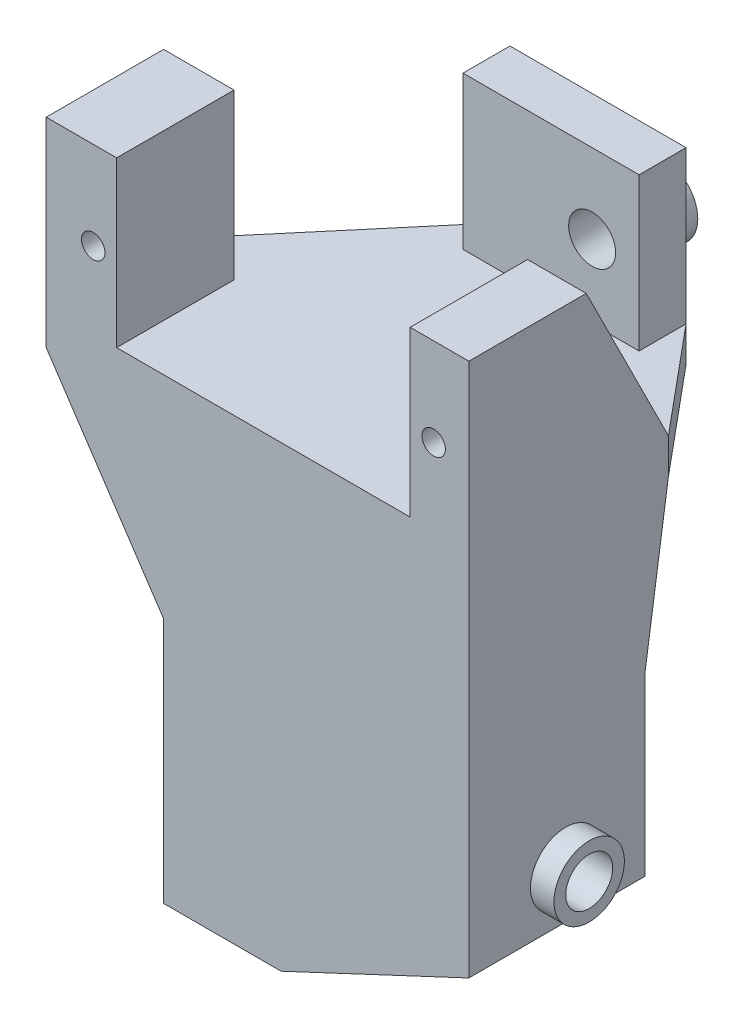
SolidWorks part; units mm, degrees
ref_plane "Front Plane" through (0, 0, 0) normal (0, 0, 1) x (1, 0, 0)
ref_plane "Top Plane" through (0, 0, 0) normal (0, 1, 0) x (1, 0, 0)
ref_plane "Right Plane" through (0, 0, 0) normal (1, 0, 0) x (0, 0, -1)
sketch "Sketch1" plane through (0, 0, 0) normal (0, 1, 0) x (1, 0, 0)
  line L1 (-25, 18) -> (25, 18)
  line L2 (-25, 18) -> (-25, -18)
  line L3 (-25, -18) -> (25, -18)
  line L4 (25, 18) -> (25, -18)
  point P4 (0, 18)
  point P6 (-25, 0)
  dimension "D1" = 50
  dimension "D2" = 36
extrude "Boss-Extrude1" add sketch "Sketch1" along normal blind 3
sketch "Sketch2" plane through (0, 3, 0) normal (0, 1, 0) x (1, 0, 0)
  line L0 (-25, -18) -> (25, -18) construction
  line L1 (25, -8) -> (20, -8)
  line L2 (25, -8) -> (25, 2)
  line L3 (25, 2) -> (20, 2)
  line L4 (20, -8) -> (20, 2)
  line L5 (-5, -8) -> (-11, -8)
  line L6 (-5, -8) -> (-5, 2)
  line L7 (-5, 2) -> (-11, 2)
  line L8 (-11, -8) -> (-11, 2)
  line L9 (25, -18) -> (25, 18) construction
  dimension "D1" = 25
  dimension "D2" = 10
  dimension "D3" = 10
  dimension "D4" = 5
  dimension "D5" = 0
  dimension "D6" = 10
  dimension "D7" = 6
extrude "Boss-Extrude2" add sketch "Sketch2" along normal blind 14
sketch "Sketch3" plane through (0, 3, 0) normal (0, 1, 0) x (1, 0, 0)
  line L0 (20, -8) -> (25, -8) construction
  line L1 (2.5, 14) -> (17.5, 14)
  line L2 (2.5, 14) -> (2.5, 18)
  line L3 (2.5, 18) -> (17.5, 18)
  line L4 (17.5, 14) -> (17.5, 18)
  line L5 (25, 2) -> (25, 18) construction
  dimension "D1" = 22
  dimension "D2" = 4
  dimension "D3" = 15
  dimension "D4" = 7.5
extrude "Boss-Extrude3" add sketch "Sketch3" along normal blind 13
sketch "Sketch4" plane through (0, 0, -18) normal (0, 0, -1) x (-1, 0, 0)
  line L0 (-25, 3) -> (-25, 0) construction
  line L2 (-25, 3) -> (-17.5, 3) construction
  circle A0 centre (-13.5, 9.25) radius 3
  dimension "D1" = 11.5
  dimension "D2" = 6.25
  dimension "D3" = 6
extrude "Boss-Extrude4" add sketch "Sketch4" along normal blind 2 contours A0
sketch "Sketch5" plane through (0, 0, -20) normal (0, 0, -1) x (-1, 0, 0)
  circle A0 centre (-13.5, 9.25) radius 2
  dimension "D1" = 4
extrude "Cut-Extrude1" cut sketch "Sketch5" against normal blind 12
sketch "Sketch6" plane through (0, 3, 0) normal (0, 1, 0) x (1, 0, 0)
  line L0 (-11, 2) -> (-11, 18)
  line L1 (2.5, 18) -> (-25, 18) construction
  line L2 (-11, 18) -> (-25, 18)
  line L3 (-25, 18) -> (-25, -18)
  line L4 (-25, -18) -> (25, -18)
  line L5 (25, -18) -> (25, -8)
  line L6 (25, -8) -> (-11, -8)
  line L7 (-11, -8) -> (-11, 2)
extrude "Cut-Extrude2" cut sketch "Sketch6" against normal blind 11
sketch "Sketch15" plane through (0, 0, 8) normal (0, 0, 1) x (1, 0, 0)
  line L1 (-5, 17) -> (-5, 3) construction
  line L4 (20, 3) -> (-5, 3) construction
  circle A0 centre (-7, 9.5) radius 1
  circle A1 centre (22, 9.5) radius 1
  dimension "D1" = 2
  dimension "D4" = 2
  dimension "D2" = 6.5
  dimension "D3" = 29
extrude "Cut-Extrude9" cut sketch "Sketch15" against normal blind 6
sketch "Sketch16" plane through (0, 0, 8) normal (0, 0, 1) x (1, 0, 0)
  line L0 (25, 17) -> (25, 0) construction
  line L1 (-11, 0) -> (25, 0)
  line L2 (-11, 0) -> (-11, -36)
  line L3 (-11, -36) -> (25, -36)
  line L4 (25, 0) -> (25, -36)
  dimension "D1" = 36
extrude "Boss-Extrude8" add sketch "Sketch16" against normal blind 2
sketch "Sketch18" plane through (25, 0, 0) normal (1, 0, 0) x (0, 0, -1)
  line L0 (-6, -28.5) -> (7, -28.5)
  line L1 (-6, -36) -> (-6, 0) construction
  line L2 (7, -28.5) -> (7, -13.5)
  line L3 (7, -13.5) -> (-6, -13.5)
  line L4 (-6, -13.5) -> (-6, -28.5)
  line L6 (-6, -36) -> (-8, -36) construction
  dimension "D1" = 13
  dimension "D2" = 15
  dimension "D3" = 7.5
extrude "Boss-Extrude9" add sketch "Sketch18" against normal blind 4
sketch "Sketch19" plane through (0, 0, 6) normal (0, 0, -1) x (-1, 0, 0)
  line L0 (11, -36) -> (-25, -36) construction
  line L1 (-9, -36) -> (1, -36)
  line L2 (-9, -36) -> (-9, -31)
  line L3 (-9, -31) -> (1, -31)
  line L4 (1, -36) -> (1, -31)
  line L5 (-25, -36) -> (-25, -28.5) construction
  line L6 (-9, -6) -> (1, -6)
  line L7 (-9, -6) -> (-9, 0)
  line L8 (-9, 0) -> (1, 0)
  line L9 (1, -6) -> (1, 0)
  line L10 (-25, 0) -> (11, 0) construction
  dimension "D1" = 26
  dimension "D2" = 10
  dimension "D3" = 5
  dimension "D4" = 25
extrude "Boss-Extrude10" add sketch "Sketch19" along normal blind 13
sketch "Sketch20" plane through (-1, 0, 0) normal (-1, 0, 0) x (0, 0, 1)
  line L0 (-7, -31) -> (6, -31) construction
  line L1 (6, -6) -> (6, 0) construction
  circle A0 centre (-0.5, -4) radius 1.25
  circle A1 centre (-0.5, -33) radius 1.25
  point P8 (0, 0)
  dimension "D1" = 2
  dimension "D3" = 6.5
  dimension "D4" = 2.5
  dimension "D2" = 29
extrude "Cut-Extrude10" cut sketch "Sketch20" against normal blind 13
sketch "Sketch21" plane through (25, 0, 0) normal (1, 0, 0) x (0, 0, -1)
  line L0 (-6, -36) -> (-6, -28.5) construction
  line L1 (-6, -28.5) -> (7, -28.5) construction
  circle A0 centre (0.25, -24.5) radius 2
  circle A1 centre (0.25, -24.5) radius 3
  dimension "D1" = 6.25
  dimension "D2" = 4
  dimension "D3" = 4
  dimension "D4" = 6
extrude "Boss-Extrude11" add sketch "Sketch21" along normal blind 2
sketch "Sketch22" plane through (25, 0, 0) normal (1, 0, 0) x (0, 0, -1)
  circle A0 centre (0.25, -24.5) radius 2
extrude "Cut-Extrude11" cut sketch "Sketch22" against normal blind 12
sketch "Sketch23" plane through (0, 0, 6) normal (0, 0, -1) x (-1, 0, 0)
  line L1 (11, -36) -> (1, -36)
  line L2 (11, -36) -> (11, 0)
  line L3 (11, 0) -> (1, 0)
  line L4 (1, -36) -> (1, 0)
extrude "Cut-Extrude12" cut sketch "Sketch23" against normal through all
sketch "Sketch24" plane through (0, 3, 0) normal (0, 1, 0) x (1, 0, 0)
  line L0 (-11, 2) -> (2.5, 18)
  line L1 (2.5, 18) -> (-11, 18)
  line L2 (-11, 18) -> (-11, 2)
extrude "Cut-Extrude13" cut sketch "Sketch24" against normal blind 12
sketch "Sketch25" plane through (0, 0, 8) normal (0, 0, 1) x (1, 0, 0)
  line L0 (-11, 0) -> (-1, -15)
  line L1 (-1, 0) -> (-1, -36) construction
  line L2 (-1, -15) -> (-1, 0)
  line L3 (-1, 0) -> (-11, 0)
  dimension "D1" = 15
extrude "Boss-Extrude12" add sketch "Sketch25" against normal up to surface (2 mm away) up to face at (14.6667, -19.1667, 6)
sketch "Sketch26" plane through (25, 0, 0) normal (1, 0, 0) x (0, 0, -1)
  line L0 (7, -13.5) -> (9, 0)
  line L1 (-6, 0) -> (18, 0) construction
  line L2 (9, 0) -> (9, 3)
  line L3 (2, 3) -> (18, 3) construction
  line L4 (9, 3) -> (2, 17)
  line L5 (2, 17) -> (2, 3)
  line L6 (2, 3) -> (2, 0)
  line L7 (7, 0) -> (-6, 0) construction
  line L8 (2, 0) -> (-6, 0)
  line L9 (-6, 0) -> (-6, -13.5)
  line L10 (7, -13.5) -> (-6, -13.5) construction
  line L11 (-6, -13.5) -> (7, -13.5)
  dimension "D1" = 15
extrude "Boss-Extrude13" add sketch "Sketch26" against normal blind 2
sketch "Sketch27" plane through (9, 0, 0) normal (1, 0, 0) x (0, 0, -1)
  line L0 (7, 0) -> (18, 0)
  line L1 (18, 0) -> (7, -6)
  line L2 (7, -6) -> (7, 0)
  point P5 (18, 0)
extrude "Boss-Extrude14" add sketch "Sketch27" against normal blind 2
sketch "Sketch28" plane through (0, 3, 0) normal (0, 1, 0) x (1, 0, 0)
  line L0 (17.5, 18) -> (25, 9)
  line L1 (25, 9) -> (25, 18)
  line L2 (25, 18) -> (17.5, 18)
extrude "Cut-Extrude14" cut sketch "Sketch28" against normal blind 12
sketch "Sketch30" plane through (0, 0, 6) normal (0, 0, -1) x (-1, 0, 0)
  line L0 (-25, -28.5) -> (-9, -36)
  line L1 (-9, -36) -> (-25, -36)
  line L2 (-25, -36) -> (-25, -28.5)
extrude "Cut-Extrude15" cut sketch "Sketch30" against normal blind 12
sketch "Sketch31" plane through (0, 0, 0) normal (0, -1, 0) x (1, 0, 0)
  line L0 (23, 6) -> (9, 6) construction
  line L1 (17.5, -18) -> (15.5, -18)
  line L2 (17.5, -18) -> (17.5, 6)
  line L3 (17.5, 6) -> (15.5, 6)
  line L4 (15.5, -18) -> (15.5, 6)
  dimension "D1" = 2
extrude "Boss-Extrude15" add sketch "Sketch31" along normal blind 6
sketch "Sketch32" plane through (15.5, 0, 0) normal (-1, 0, 0) x (0, 0, 1)
  line L0 (-18, 0) -> (-18, -6)
  line L1 (-18, -6) -> (-18, 0) construction
  line L2 (6, -6) -> (-18, -6) construction
  line L3 (-18, -6) -> (6, -6)
  line L4 (6, -6) -> (-18, 0)
extrude "Cut-Extrude16" cut sketch "Sketch32" against normal blind 6
